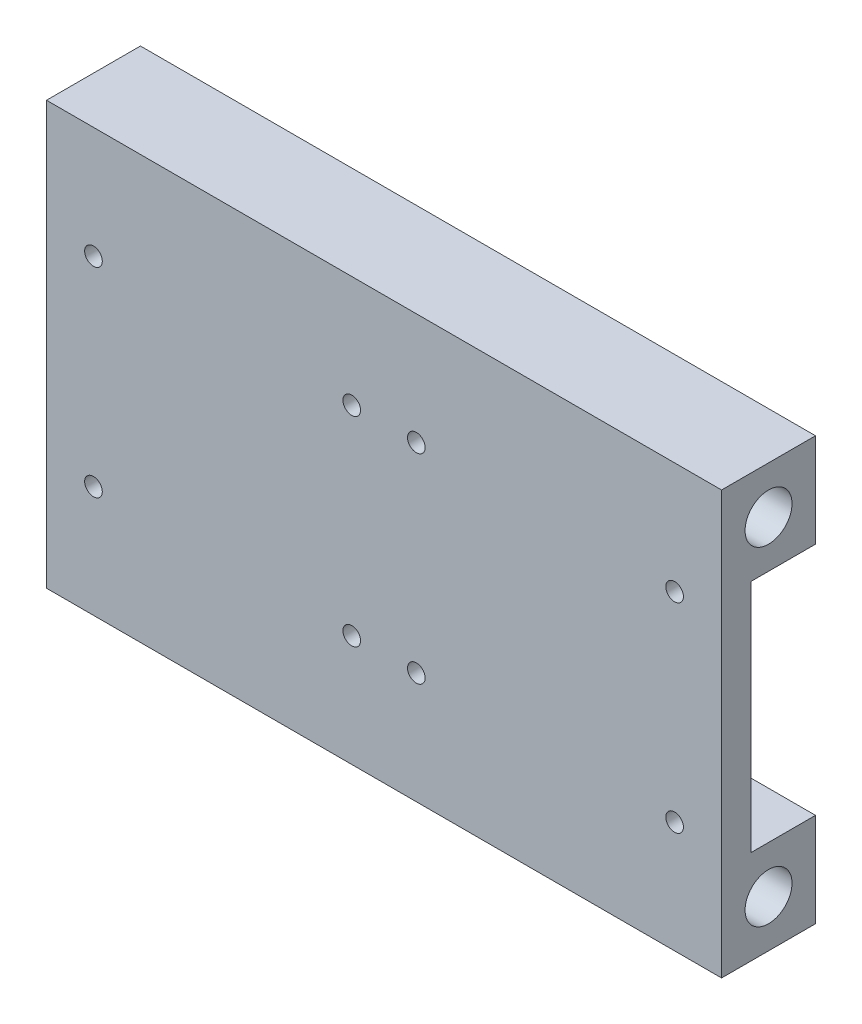
SolidWorks part; units mm, degrees
ref_plane "Front Plane" through (0, 0, 0) normal (0, 0, 1) x (1, 0, 0)
ref_plane "Top Plane" through (0, 0, 0) normal (0, 1, 0) x (1, 0, 0)
ref_plane "Right Plane" through (0, 0, 0) normal (1, 0, 0) x (0, 0, -1)
sketch "Sketch1" plane through (0, 0, 0) normal (0, 0, 1) x (1, 0, 0)
  line L0 (0, 0) -> (0, 40)
  line L1 (0, 40) -> (115, 40)
  line L2 (115, 40) -> (115, 0)
  line L4 (110, 34) -> (110, 6) construction
  line L5 (0, 0) -> (5, 0)
  line L6 (5, 0) -> (55, 0)
  line L7 (60, 0) -> (110, 0)
  line L8 (110, 0) -> (115, 0)
  line L9 (5, 34) -> (5, 40) construction
  line L10 (55, 0) -> (60, 0)
  line L11 (5, 40) -> (11, 34) construction
  line L12 (11, 34) -> (5, 34) construction
  line L13 (5, 0) -> (5, 6) construction
  line L14 (5, 6) -> (11, 6) construction
  line L15 (5, 34) -> (5, 6) construction
  line L16 (5, 0) -> (11, 6) construction
  line L17 (110, 40) -> (104, 34) construction
  line L18 (104, 34) -> (110, 34) construction
  line L19 (110, 34) -> (110, 40) construction
  line L20 (110, 0) -> (104, 6) construction
  line L21 (104, 6) -> (110, 6) construction
  line L22 (110, 6) -> (110, 0) construction
  line L26 (60, 0) -> (60, 40) construction
  line L27 (55, 40) -> (49, 34) construction
  line L28 (55, 0) -> (55, 40) construction
  line L29 (49, 34) -> (55, 34) construction
  line L30 (60, 40) -> (66, 34) construction
  line L31 (66, 34) -> (60, 34) construction
  line L32 (55, 0) -> (49, 6) construction
  line L33 (49, 6) -> (55, 6) construction
  line L34 (60, 0) -> (66, 6) construction
  line L35 (66, 6) -> (60, 6) construction
  point P2 (0, 0)
  point P26 (107, 37)
  point P35 (107, 3)
  point P36 (63, 3)
  point P37 (63, 37)
  point P38 (52, 37)
  point P39 (52, 3)
  point P40 (8, 3)
  point P41 (8, 37)
  dimension "D5" = 6
  dimension "D1" = 115
  dimension "D2" = 40
  dimension "D3" = 5
extrude "Boss-Extrude1" add sketch "Sketch1" along normal blind 5
sketch "Sketch5" plane through (115, 0, 0) normal (1, 0, 0) x (0, 0, -1)
  line L0 (-5, 40) -> (11, 40)
  line L3 (-5, 0) -> (11, 0)
  line L4 (3, 56) -> (3, 40) construction
  line L6 (-5, 40) -> (-5, 56)
  line L7 (-5, 56) -> (11, 56)
  line L8 (11, 56) -> (11, 40)
  line L12 (11, 0) -> (11, -16)
  line L13 (11, -16) -> (-5, -16)
  line L14 (-5, -16) -> (-5, 0)
  line L15 (3, 0) -> (3, -16) construction
  circle A0 centre (3, -8) radius 4
  circle A1 centre (3, 48) radius 4
  dimension "D2" = 8
  dimension "D1" = 16
extrude "Boss-Extrude2" add sketch "Sketch5" against normal up to surface (115 mm away) up to face at (0, 20, 2.5)
sketch "Sketch8" plane through (0, 0, 0) normal (0, 0, -1) x (-1, 0, 0)
  line L1 (-60, 0) -> (-66, 6) construction
  line L2 (-55, 0) -> (-49, 6) construction
  circle A0 centre (-107, 37) radius 1.5
  circle A1 centre (-63, 37) radius 1.5
  circle A2 centre (-52, 37) radius 1.5
  circle A3 centre (-8, 37) radius 1.5
  circle A4 centre (-8, 3) radius 1.5
  circle A6 centre (-63, 3) radius 1.5
  circle A7 centre (-52, 3) radius 1.5
  circle A8 centre (-107, 3) radius 1.5
  dimension "D1" = 3
extrude "Cut-Extrude1" cut sketch "Sketch8" against normal up to surface (5 mm away) up to face at (57.5, 20, 5)
equation "\"board_length\"= 260mm"
equation "\"board_height\"= 200mm"
equation "\"board_width\"= 16.5mm"
equation "\"token_thickness\"= 7mm"
equation "\"token_diameter\"= 32mm"
equation "\"board_side_lower_height\"= 55mm"
equation "\"board_side_height\"= 156.5mm"
equation "\"board_side_length\"= 100mm"
equation "\"board_slot_width\"= \"board_length\" / 7"
equation "\"token_ridge\"= ( \"token_thickness\" - 4mm ) / 2"
equation "\"token_ridge_width\"= 1.5mm"
equation "\"25T_outer_diameter\"= 20mm"
equation "\"25T_inner_diameter\"= 9mm"
equation "\"2T_screw_distance\" = 14mm"
equation "\"2T_outer_thickness\"= 2mm"
equation "\"2T_inner_thickness\"= 4.5mm"
equation "\"MG996R_outer_length\"= 54mm"
equation "\"MG996R_inner_length\"= 40mm"
equation "\"MG996R_width\"= 20mm"
equation "\"MG996R_height\" = 26.6mm"
equation "\"MG996R_full_height\"= 45.7mm"
equation "\"MG996R_full_width\"= 55.5mm"
equation "\"MG996R_screw_distance\"= 10mm"
equation "\"magnet_diameter\" = 10mm"
equation "\"magnet_thickness\"= 2mm"
equation "\"dispenser_barrel_margin\"= 2.5mm"
equation "\"dispenser_wheel_width\"= \"token_thickness\" + 5mm"
equation "\"dispenser_cover_margin\"= 3.0mm"
equation "\"dispenser_cover_thickness\"= 5.0mm"
equation "\"MG996R_major_axis_distance\"= 34.3mm"
equation "\"MG996R_major_screw_distance\"= 48.6mm"
equation "\"MG996R_minor_screw_distance\"= 9.9mm"
equation "\"MG996R_mid_height\"= 37.5mm"
equation "\"dispenser_slope\"= 30deg"
equation "\"dispenser_cover_length\"= 20mm"
equation "\"dispenser_carrier_width\" = 3.5mm"
equation "\"dispenser_carrier_height\"= 50mm"
equation "\"carrier_width\"= \"shaft_diameter\" * 2"
equation "\"shaft_diameter\"= 8mm"
equation "\"carrier_thickness\"=16"
equation "\"D1@Boss-Extrude1\"=\"carrier_width\""
equation "\"D1@Sketch1\"=\"MG996R_outer_length\"*2+\"dispenser_cover_margin\"+4mm"
equation "\"D2@Sketch1\"=\"dispenser_carrier_height\"-\"dispenser_cover_thickness\"/sin(\"dispenser_slope\")"
equation "\"D3@Sketch1\"=\"dispenser_cover_thickness\""
equation "\"D1@Sketch5\"=\"carrier_width\""
equation "\"D2@Sketch5\"=\"shaft_diameter\""
